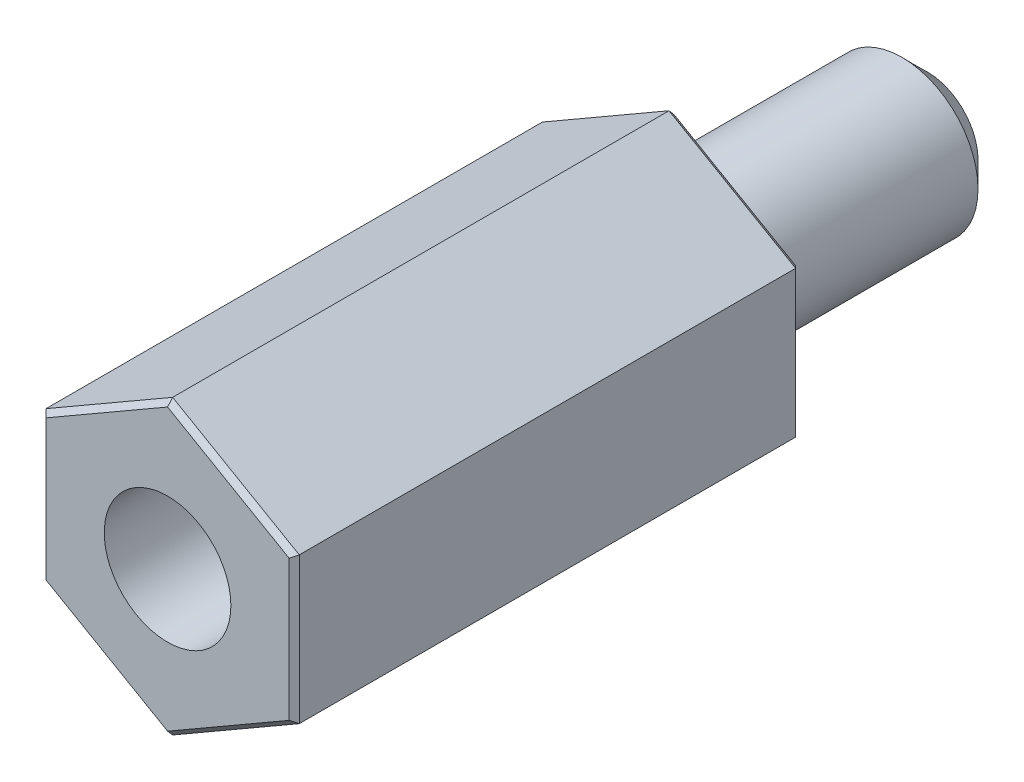
SolidWorks part; units mm, degrees
ref_plane "Płaszczyzna przednia" through (0, 0, 0) normal (0, 0, 1) x (1, 0, 0)
ref_plane "Płaszczyzna górna" through (0, 0, 0) normal (0, 1, 0) x (1, 0, 0)
ref_plane "Płaszczyzna prawa" through (0, 0, 0) normal (1, 0, 0) x (0, 0, -1)
sketch "Szkic1" plane through (0, 0, 0) normal (0, 0, 1) x (1, 0, 0)
  line L1 (0, 2.8868) -> (-2.5, 1.4434)
  line L2 (-2.5, 1.4434) -> (-2.5, -1.4434)
  line L3 (-2.5, -1.4434) -> (0, -2.8868)
  line L4 (0, -2.8868) -> (2.5, -1.4434)
  line L5 (2.5, -1.4434) -> (2.5, 1.4434)
  line L6 (2.5, 1.4434) -> (0, 2.8868)
  circle A0 centre (0, 0) radius 2.5 construction
  dimension "D1" = 5
extrude "Dodanie-wyciągnięcie1" add sketch "Szkic1" along normal blind 10
sketch "Szkic2" plane through (0, 0, 0) normal (0, 0, -1) x (-1, 0, 0)
  circle A0 centre (0, 0) radius 1.5
  dimension "D1" = 3
extrude "Dodanie-wyciągnięcie2" add sketch "Szkic2" along normal blind 5
chamfer "Sfazowanie2" distance 0.5 angle 45 1 edges at (-1.5, 0, -5)
hole_wizard "Otwór gwintowany M31" positions "Szkic27" profile "Szkic26" tap size "M3" standard "ISO"
sketch "Szkic27" plane through (0, 0, 10) normal (0, 0, 1) x (1, 0, 0)
  point P0 (0, 0)
sketch "Szkic26" plane through (0, 0, 10) normal (1, 0, 0) x (0, -1, 0)
  line L0 (0, 0) -> (0, 8.7511)
  line L1 (0, 8.7511) -> (1.25, 8)
  line L2 (1.25, 8) -> (1.25, 0)
  line L5 (1.25, 0) -> (0, 0)
  line L10 (0, 8.7511) -> (-1.25, 8) construction
  line L11 (0, -6.35) -> (0, 107.95) construction
  dimension "Średnica wiertła gwintu" = 2.5
  dimension "Głębokość otworu gwintowanego" = 8
  dimension "Kąt wiertła" = 118
cosmetic thread "Gwint otworu1" parameters "D1"=8, "D2"=3
chamfer "Sfazowanie3" distance 0.1 angle 45 12 edges at (2.5, 0, 10) (1.25, -2.1651, 10) (-1.25, -2.1651, 10) (-2.5, 0, 10) (-1.25, 2.1651, 10) (1.25, 2.1651, 10) (1.25, -2.1651, 0) (2.5, 0, 0) (1.25, 2.1651, 0) (-1.25, 2.1651, 0) (-1.25, -2.1651, 0) (-2.5, 0, 0)
